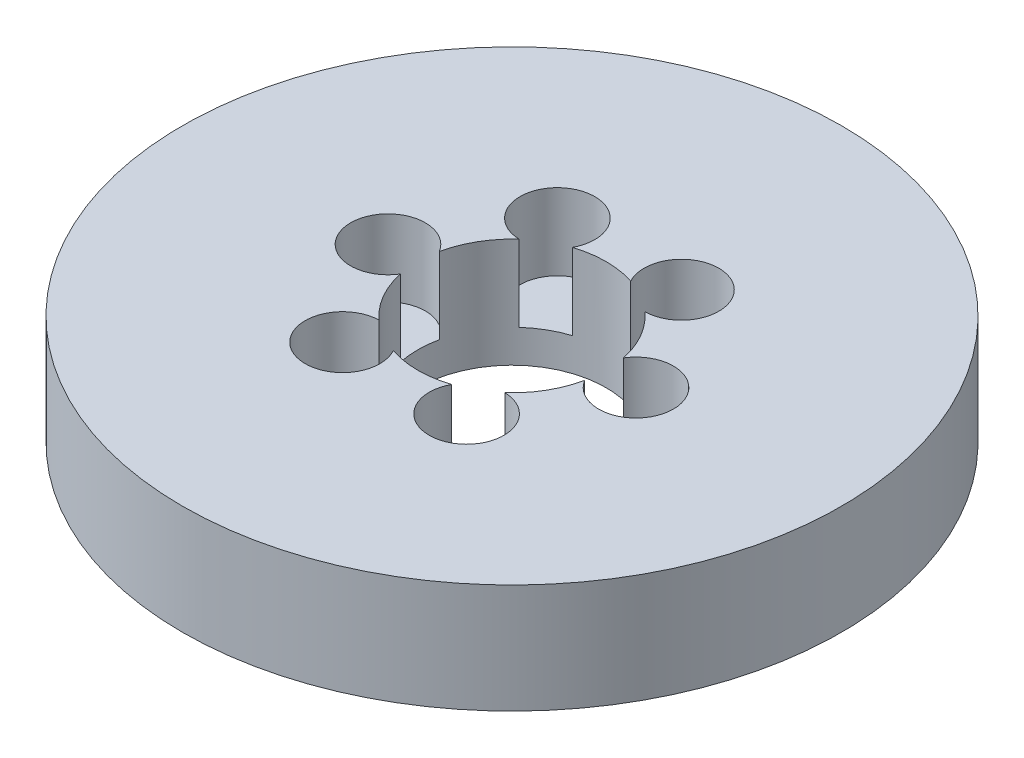
SolidWorks part; units mm, degrees
ref_plane "Front Plane" through (0, 0, 0) normal (0, 0, 1) x (1, 0, 0)
ref_plane "Top Plane" through (0, 0, 0) normal (0, 1, 0) x (1, 0, 0)
ref_plane "Right Plane" through (0, 0, 0) normal (1, 0, 0) x (0, 0, -1)
sketch "Sketch1" plane through (0, 0, 0) normal (0, 1, 0) x (1, 0, 0)
  circle A0 centre (0, 0) radius 87.5
  dimension "FLANGE_OD" = 175
extrude "Boss-Extrude1" add sketch "Sketch1" along normal blind 29
sketch "Sketch2" plane through (0, 0, 0) normal (0, 1, 0) x (1, 0, 0)
  circle A0 centre (0, 0) radius 25
  dimension "BORE_D" = 50
extrude "Cut-Extrude1" cut sketch "Sketch2" along normal through all
sketch "Sketch3" plane through (0, 29, 0) normal (0, 1, 0) x (1, 0, 0)
  circle A0 centre (0, 0) radius 32.9306 construction
  circle A1 centre (-32.9306, 0) radius 9.9217
  dimension "BOLT_D" = 19.8435
  dimension "BOLT_PCD" = 65.8611
extrude "Cut-Extrude2" cut sketch "Sketch3" against normal blind 20.2726
pattern_circular "CirPattern1" count 6 over 360 about axis through (0, 0, 0) along (0, 1, 0) of "Cut-Extrude2"
